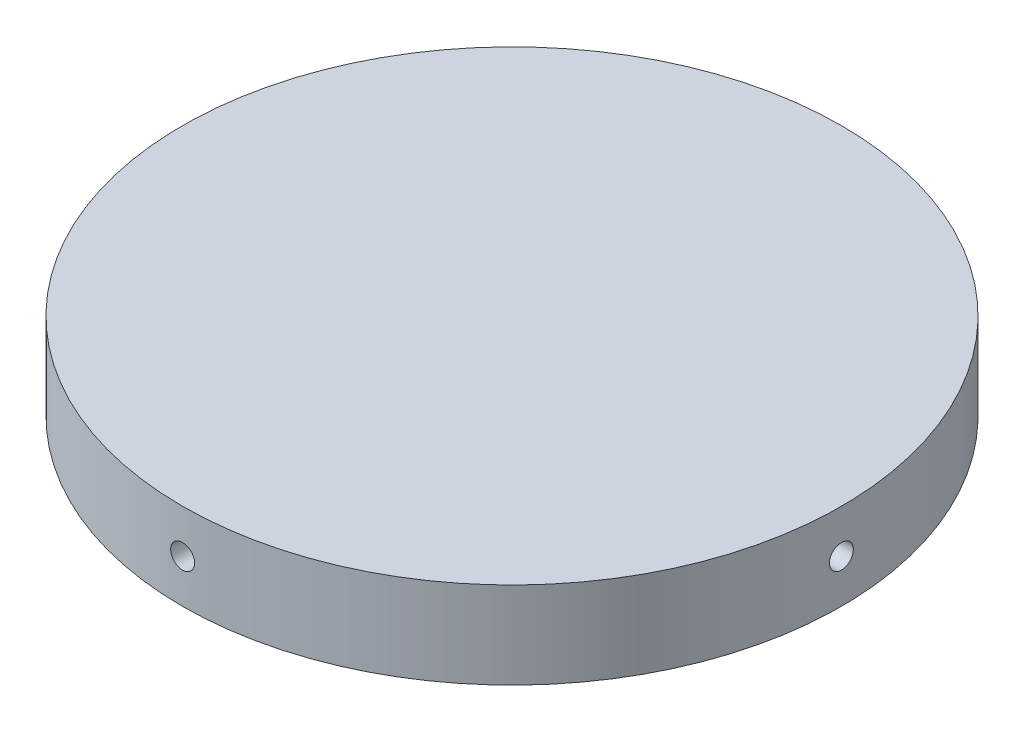
SolidWorks part; units mm, degrees
material "6061 Alloy"
ref_plane "Front Plane" through (0, 0, 0) normal (0, 0, 1) x (1, 0, 0)
ref_plane "Top Plane" through (0, 0, 0) normal (0, 1, 0) x (1, 0, 0)
ref_plane "Right Plane" through (0, 0, 0) normal (1, 0, 0) x (0, 0, -1)
sketch "Sketch1" plane through (0, 0, 0) normal (0, 1, 0) x (1, 0, 0)
  circle A0 centre (0, 0) radius 48.26
  dimension "D1" = 96.52
extrude "Bulkhead Extrusion" add sketch "Sketch1" along normal blind 12.7
ref_plane "Plane1" through (0, 0, 48.26) normal (0, 0, 1) x (1, 0, 0)
sketch "Sketch2" plane through (0, 0, 48.26) normal (0, 0, 1) x (1, 0, 0)
  line L0 (0, 12.7) -> (0, 0) construction
  line L1 (48.26, 12.7) -> (-48.26, 12.7) construction
  circle A0 centre (0, 6.35) radius 1.7526
  dimension "D1" = 3.5052
extrude "Screw Hole" cut sketch "Sketch2" against normal blind 19.05
pattern_circular "CirPattern1" count 4 over 360 about axis through (0, 12.7, 0) along (0, -1, 0) of "Screw Hole" reverse direction yes
